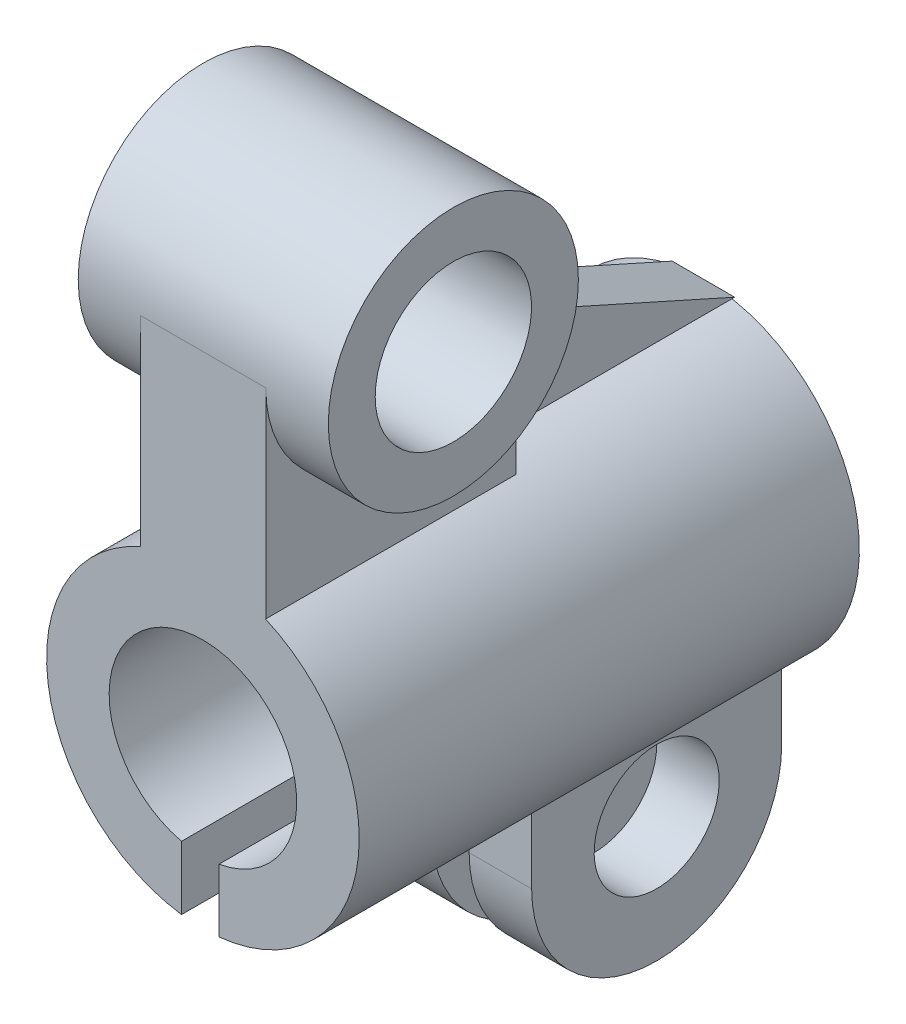
SolidWorks part; units mm, degrees
ref_plane "Ön Düzlem" through (0, 0, 0) normal (0, 0, 1) x (1, 0, 0)
ref_plane "Üst Düzlem" through (0, 0, 0) normal (0, 1, 0) x (1, 0, 0)
ref_plane "Sağ Düzlem" through (0, 0, 0) normal (1, 0, 0) x (0, 0, -1)
sketch "Çizim1" plane through (0, 0, 0) normal (0, 0, 1) x (1, 0, 0)
  circle A0 centre (-27.7278, 20.6509) radius 15
  circle A1 centre (-27.7278, 20.6509) radius 25
  dimension "D1" = 30
  dimension "D2" = 50
extrude "Yükseklik-Ekstrüzyon1" add sketch "Çizim1" along normal blind 80
sketch "Çizim3" plane through (0, 0, 0) normal (0, 0, -1) x (-1, 0, 0)
  line L1 (15.1496, -0.5342) -> (41.1496, -0.5342)
  line L2 (15.1496, -0.5342) -> (15.1496, -32.5342)
  line L3 (15.1496, -32.5342) -> (41.1496, -32.5342)
  line L4 (41.1496, -0.5342) -> (41.1496, -32.5342)
  dimension "D1" = 26
  dimension "D2" = 32
extrude "Yükseklik-Ekstrüzyon3" add sketch "Çizim3" against normal blind 40 contours L2 L1 L4 L3
fillet "Radyus2" 2 edges at (-28.1496, -32.5342, 0) (-28.1496, -32.5342, 40) type full round first side face at (-30.5692, -4.1399, 0) second side face at (-30.7317, -14.1385, 40) middle face at (-28.1496, -32.5342, 20)
sketch "Çizim5" plane through (0, 0, 0) normal (0, 0, -1) x (-1, 0, 0)
  line L0 (15.1496, -32.5342) -> (41.1496, -32.5342) construction
  line L1 (25.1496, -32.5342) -> (31.1496, -32.5342)
  line L2 (25.1496, -32.5342) -> (25.1496, 11.4721)
  line L3 (25.1496, 11.4721) -> (31.1496, 11.4721)
  line L4 (31.1496, -32.5342) -> (31.1496, 11.4721)
  line L5 (41.1496, -32.5342) -> (41.1496, -12.5342) construction
  dimension "D1" = 6
  dimension "D2" = 10
extrude "Kes-Ekstrüzyon1" cut sketch "Çizim5" against normal through all
sketch "Çizim7" plane through (-41.1496, 0, 0) normal (-1, 0, 0) x (0, 0, 1)
  circle A0 centre (20, -12.5342) radius 10
  dimension "D1" = 20
extrude "Kes-Ekstrüzyon2" cut sketch "Çizim7" against normal through all both and the other way through all
sketch "Çizim9" plane through (0, 0, 80) normal (0, 0, 1) x (1, 0, 0)
  line L1 (-37.6731, 43.5876) -> (-17.6731, 43.5876)
  line L2 (-37.6731, 43.5876) -> (-37.6731, 75.5876)
  line L3 (-37.6731, 75.5876) -> (-17.6731, 75.5876)
  line L4 (-17.6731, 43.5876) -> (-17.6731, 75.5876)
  arc A1 (-25.1496, -4.2158) -> (-31.1496, -4.1138) centre (-27.7278, 20.6509) ccw construction
  dimension "D1" = 20
  dimension "D2" = 32
extrude "Yükseklik-Ekstrüzyon4" add sketch "Çizim9" against normal blind 40
ref_plane "Düzlem1" through (-27.6731, 0, 0) normal (-1, 0, 0) x (0, 0, 1)
sketch "Çizim10" plane through (-27.6731, 0, 0) normal (-1, 0, 0) x (0, 0, 1)
  line L0 (0, 45.6509) -> (40, 63.5876)
  line L2 (40, 63.5876) -> (40, 45.6396)
  line L3 (40, 45.6396) -> (0, 45.6509)
  dimension "D1" = 12
extrude "Yükseklik-Ekstrüzyon5" add sketch "Çizim10" along normal mid plane 10
sketch "Çizim11" plane through (-27.6731, 0, 0) normal (-1, 0, 0) x (0, 0, 1)
  line L0 (40, 75.5876) -> (80, 75.5876) construction
  circle A0 centre (60, 75.5876) radius 20
  circle A1 centre (60, 75.5876) radius 12.5
  dimension "D1" = 40
  dimension "D2" = 25
extrude "Yükseklik-Ekstrüzyon6" add sketch "Çizim11" along normal mid plane 40
sketch "Çizim12" plane through (-37.6731, 0, 0) normal (-1, 0, 0) x (0, 0, 1)
  line L0 (47.5, 75.5876) -> (72.5, 75.5876) construction
  circle A0 centre (60, 75.5876) radius 12.5
extrude "Kes-Ekstrüzyon3" cut sketch "Çizim12" against normal through all both and the other way through all
